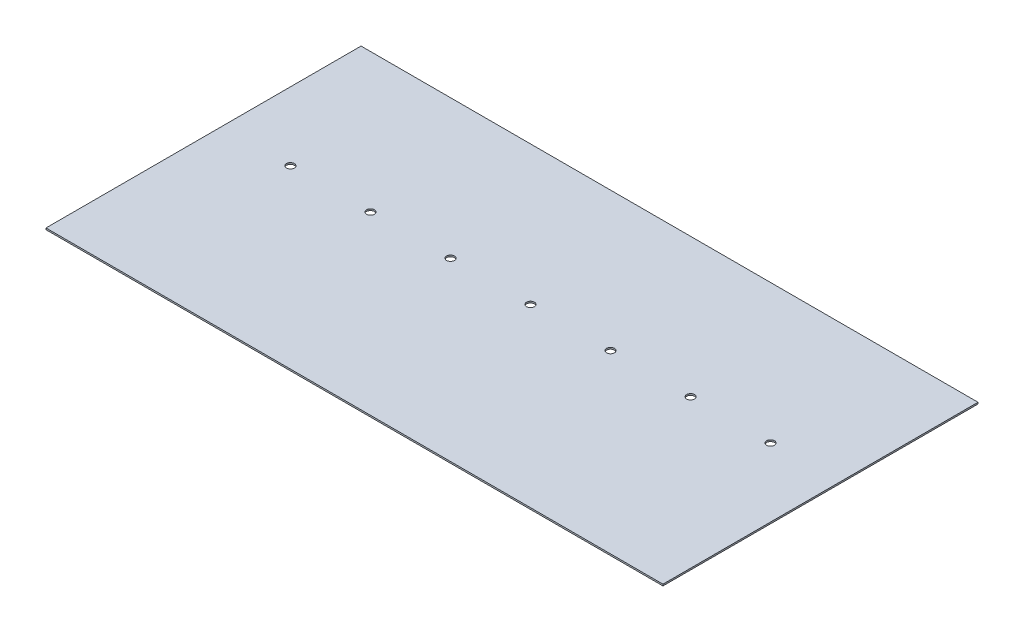
SolidWorks part; units mm, degrees
ref_plane "Front Plane" through (0, 0, 0) normal (0, 0, 1) x (1, 0, 0)
ref_plane "Top Plane" through (0, 0, 0) normal (0, 1, 0) x (1, 0, 0)
ref_plane "Right Plane" through (0, 0, 0) normal (1, 0, 0) x (0, 0, -1)
sketch "Sketch1" plane through (0, 0, 0) normal (0, 1, 0) x (1, 0, 0)
  line L0 (195.834, -199.9996) -> (195.834, -88.2396) construction
  line L1 (0, 0) -> (391.668, 0)
  line L2 (0, 0) -> (0, -199.9996)
  line L3 (0, -199.9996) -> (391.668, -199.9996)
  line L4 (391.668, 0) -> (391.668, -199.9996)
  line L5 (195.834, -88.2396) -> (391.668, -88.2396) construction
  line L6 (195.834, -88.2396) -> (0, -88.2396) construction
  circle A0 centre (195.834, -88.2396) radius 2.5
  circle A1 centre (145.034, -88.2396) radius 2.5
  circle A2 centre (94.234, -88.2396) radius 2.5
  circle A3 centre (43.434, -88.2396) radius 2.5
  circle A4 centre (195.834, -88.2396) radius 2.5
  circle A5 centre (145.034, -88.2396) radius 2.5
  circle A6 centre (94.234, -88.2396) radius 2.5
  circle A7 centre (246.634, -88.2396) radius 2.5
  circle A8 centre (195.834, -88.2396) radius 2.5
  circle A9 centre (145.034, -88.2396) radius 2.5
  circle A10 centre (297.434, -88.2396) radius 2.5
  circle A11 centre (246.634, -88.2396) radius 2.5
  circle A12 centre (195.834, -88.2396) radius 2.5
  circle A13 centre (246.634, -88.2396) radius 2.5
  circle A14 centre (297.434, -88.2396) radius 2.5
  circle A15 centre (348.234, -88.2396) radius 2.5
  dimension "D4" = 5
  dimension "D1" = 199.9996
  dimension "D2" = 391.668
  dimension "D3" = 111.76
  dimension "D5" = 4
  dimension "D6" = 4
extrude "Boss-Extrude1" add sketch "Sketch1" against normal blind 1 contours L4 L1 L2 L3 A15 A10 A7 A3 A2 A1 A0 region at (195.834, 0, 100.0205)
ref_plane "Plane1" through (195.834, 0, 0) normal (-1, 0, 0) x (0, 0, 1)
ref_plane "Plane2" through (0, 0, 99.9998) normal (0, 0, -1) x (-1, 0, 0)
ref_plane "Plane3" through (0, 0, 88.2396) normal (0, 0, -1) x (-1, 0, 0)
